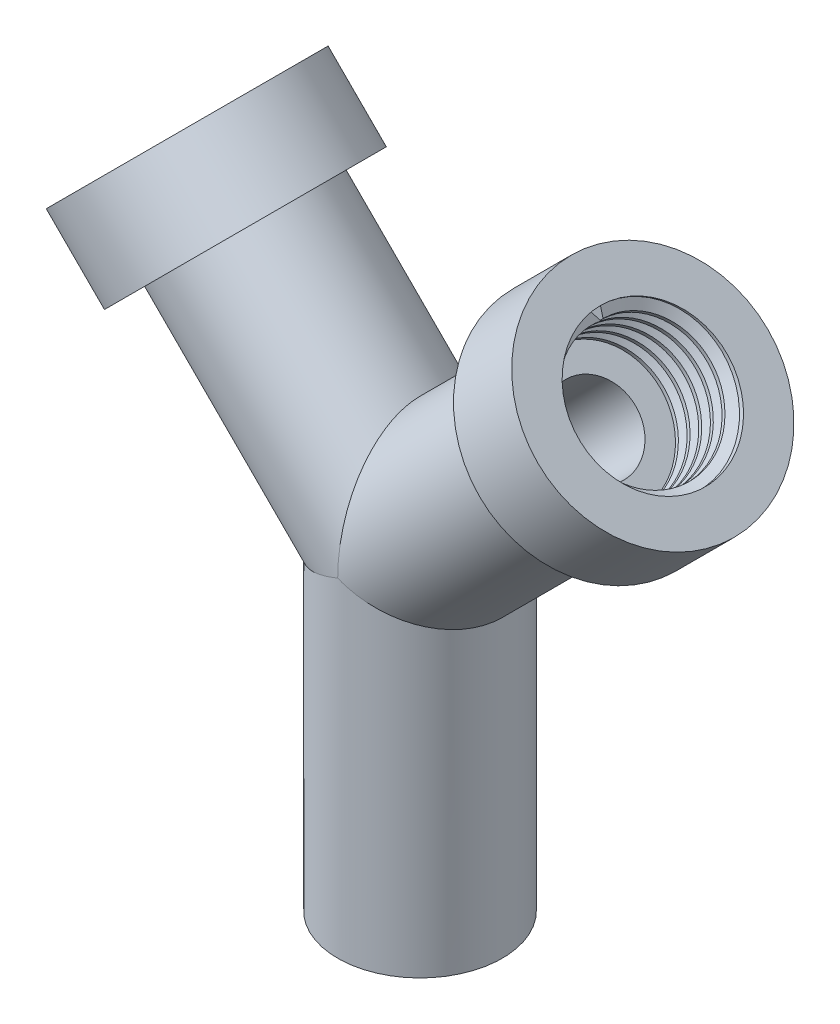
SolidWorks part; units mm, degrees
ref_plane "Front Plane" through (0, 0, 0) normal (0, 0, 1) x (1, 0, 0)
ref_plane "Top Plane" through (0, 0, 0) normal (0, 1, 0) x (1, 0, 0)
ref_plane "Right Plane" through (0, 0, 0) normal (1, 0, 0) x (0, 0, -1)
sketch "Sketch1" plane through (0, 0, 0) normal (0, 0, 1) x (1, 0, 0)
  line L0 (0, 0) -> (0, 31.6392) construction
  line L1 (0, 0) -> (13.4704, 13.4704) construction
  line L2 (13.4704, 13.4704) -> (9.4293, 17.5115)
  line L3 (8.9803, 17.9605) -> (-4.4901, 4.4901)
  line L4 (-4.4901, 4.4901) -> (0, 0)
  line L5 (0, 0) -> (13.4704, 13.4704)
  line L6 (11.2253, 15.7154) -> (17.574, 22.0641) construction
  line L7 (9.4293, 17.5115) -> (13.9194, 22.0016)
  line L8 (13.9194, 22.0016) -> (11.6743, 24.2467)
  line L9 (11.6743, 24.2467) -> (7.1842, 19.7566)
  line L10 (7.1842, 19.7566) -> (8.9803, 17.9605)
  dimension "D1" = 45
  dimension "D2" = 19.05
  dimension "D3" = 0
  dimension "D4" = 3.175
  dimension "D5" = 6.35
  dimension "D6" = 2.54
  dimension "D7" = 6.35
  dimension "D8" = 3.175
revolve "Revolve1" add sketch "Sketch1" angle 360 about L5
mirror "Mirror1" about plane through (0, 0, 0) normal (1, 0, 0) of "Revolve1"
sketch "Sketch2" plane through (0, 0, 0) normal (0, 0, 1) x (1, 0, 0)
  line L0 (0, 0) -> (0, -12.0674) construction
  line L1 (0, 0) -> (6.35, 0)
  line L2 (6.35, 0) -> (6.35, -25.4)
  line L3 (6.35, -25.4) -> (0, -25.4)
  line L4 (0, -25.4) -> (0, 0)
  dimension "D1" = 6.35
  dimension "D2" = 25.4
revolve "Revolve2" add sketch "Sketch2" angle 360 about L0
sketch "Sketch3" plane through (13.4704, 13.4704, 0) normal (0.7071, 0.7071, 0) x (0, 0, -1)
  circle A0 centre (0, 0) radius 3.175
  circle A1 centre (0, 0) radius 5.715 construction
  dimension "D2" = 6.35
  dimension "D1" = 0
extrude "Cut-Extrude1" cut sketch "Sketch3" against normal blind 19.05
mirror "Mirror2" about plane through (0, 0, 0) normal (1, 0, 0) of "Cut-Extrude1"
sketch "Sketch4" plane through (0, -25.4, 0) normal (0, -1, 0) x (1, 0, 0)
  circle A0 centre (0, 0) radius 3.175
  circle A1 centre (0, 0) radius 6.35 construction
  dimension "D2" = 6.35
  dimension "D1" = 0
extrude "Cut-Extrude2" cut sketch "Sketch4" against normal blind 25.4
thread "Thread1" pitch 1.27 method extrude profile "Thread Profile1" start angle 0, offset 0, length 0, pitch 1.27, diameter 11.43
ref_plane "Plane1" through (-22.0016, 13.9194, 0) normal (0, 0, 1) x (-0.7071, -0.7071, 0)
sketch "Thread Profile1" plane through (-22.0016, 13.9194, 0) normal (0, 0, 1) x (-0.7071, -0.7071, 0)
  line L0 (0, 0) -> (0, 1.27) construction
  line L11 (0, 0) -> (0, 1.1112)
  line L12 (0, 1.1112) -> (-0.6874, 0.7144)
  line L13 (-0.6874, 0.7144) -> (-0.6874, 0.3969)
  line L15 (-0.6874, 0.3969) -> (0, 0)
  line L17 (-0.6874, 0.5556) -> (0, 0.5556) construction
  point P2 (0, 0)
  dimension "Pitch" = 1.27
  dimension "Profile_Angle" = 60
  dimension "Profile_Land" = 0.3175
  dimension "Profile_Height" = 0.6874
thread "Thread2" pitch 1.27 method extrude profile "Thread Profile2" start angle 0, offset 0, length 0, pitch 1.27, diameter 11.43
ref_plane "Plane2" through (13.9194, 22.0016, 0) normal (0, 0, 1) x (-0.7071, 0.7071, 0)
sketch "Thread Profile2" plane through (13.9194, 22.0016, 0) normal (0, 0, 1) x (-0.7071, 0.7071, 0)
  line L0 (0, 0) -> (0, 1.27) construction
  line L11 (0, 0) -> (0, 1.1112)
  line L12 (0, 1.1112) -> (-0.6874, 0.7144)
  line L13 (-0.6874, 0.7144) -> (-0.6874, 0.3969)
  line L15 (-0.6874, 0.3969) -> (0, 0)
  line L17 (-0.6874, 0.5556) -> (0, 0.5556) construction
  point P2 (0, 0)
  dimension "Pitch" = 1.27
  dimension "Profile_Angle" = 60
  dimension "Profile_Land" = 0.3175
  dimension "Profile_Height" = 0.6874
